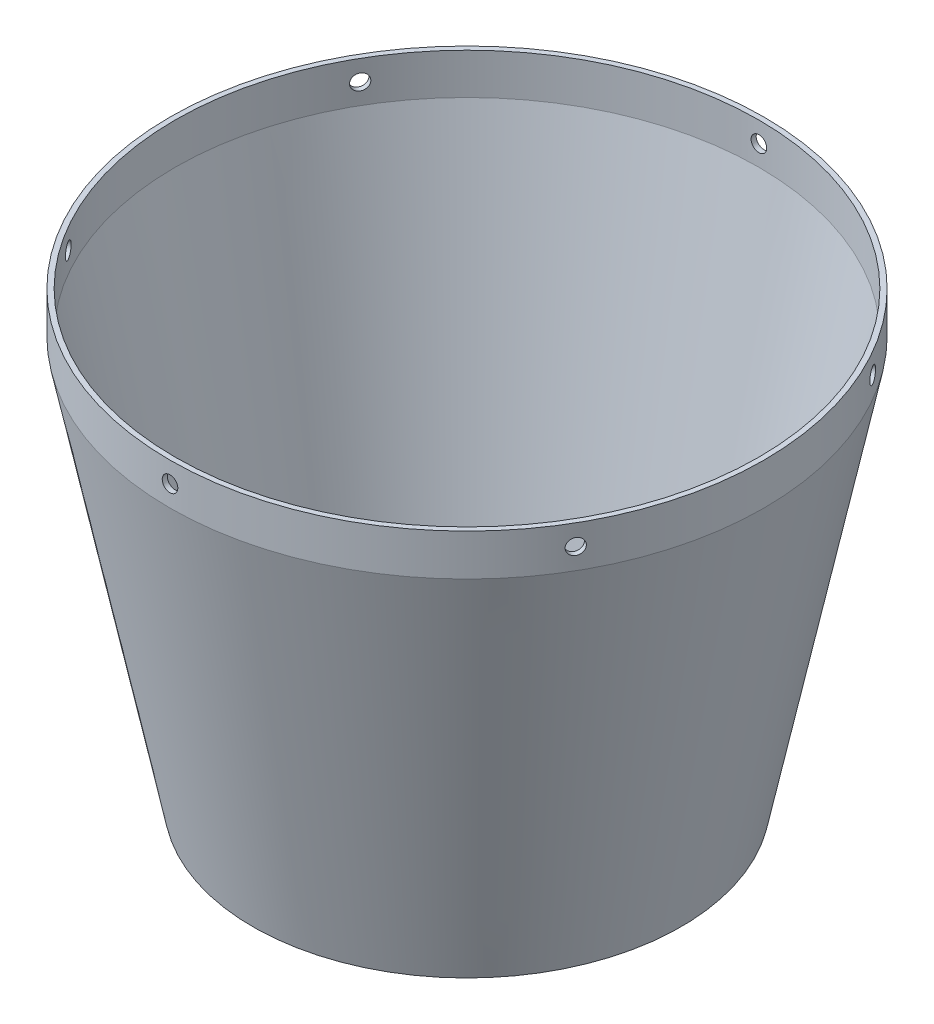
SolidWorks part; units mm, degrees
material "A-Glass Fiber"
ref_plane "Front Plane" through (0, 0, 0) normal (0, 0, 1) x (1, 0, 0)
ref_plane "Top Plane" through (0, 0, 0) normal (0, 1, 0) x (1, 0, 0)
ref_plane "Right Plane" through (0, 0, 0) normal (1, 0, 0) x (0, 0, -1)
sketch "Sketch1" plane through (0, 0, 0) normal (0, 0, 1) x (1, 0, 0)
  line L0 (0, 0) -> (0, 12.7) construction
  line L3 (0, 12.7) -> (90.4875, 12.7) construction
  line L4 (90.4875, 0) -> (90.4875, 12.7)
  line L7 (0, 0) -> (0, -123.825) construction
  line L8 (0, -123.825) -> (65.0875, -123.825) construction
  line L10 (65.0875, -123.825) -> (90.4875, 0)
  line L11 (66.3824, -125.4125) -> (92.075, -0.1611)
  line L12 (92.075, -0.1611) -> (92.075, 12.7)
  line L13 (-1.5875, 14.2875) -> (92.075, 14.2875) construction
  line L14 (-1.5875, 0) -> (-1.5875, 14.2875) construction
  line L15 (-1.5875, 0) -> (-1.5875, -125.4125) construction
  line L16 (-1.5875, -125.4125) -> (66.3824, -125.4125) construction
  line L17 (90.4875, 12.7) -> (92.075, 12.7)
  line L18 (65.0875, -123.825) -> (65.0875, -125.4125)
  line L19 (65.0875, -125.4125) -> (66.3824, -125.4125)
  line L20 (92.075, -0.1611) -> (92.075, 14.2875) construction
  point P0 (0, 0)
  dimension "D1" = 90.4875
  dimension "D2" = 12.7
  dimension "D3" = 1.5875
  dimension "D4" = 123.825
  dimension "D5" = 65.0875
revolve "Revolve1" add sketch "Sketch1" angle 360 about L7
sketch "Sketch2" plane through (0, 0, 0) normal (0, 0, 1) x (1, 0, 0)
  line L0 (0, 0) -> (0, 12.7) construction
  line L1 (92.075, 12.7) -> (-92.075, 12.7) construction
  circle A0 centre (0, 6.35) radius 2.413
  dimension "D1" = 4.826
extrude "Cut-Extrude1" cut sketch "Sketch2" against normal through all both and the other way through all
pattern_circular "CirPattern1" count 6 over 360 about axis through (0, 12.7, 0) along (0, 1, 0) of "Cut-Extrude1"
